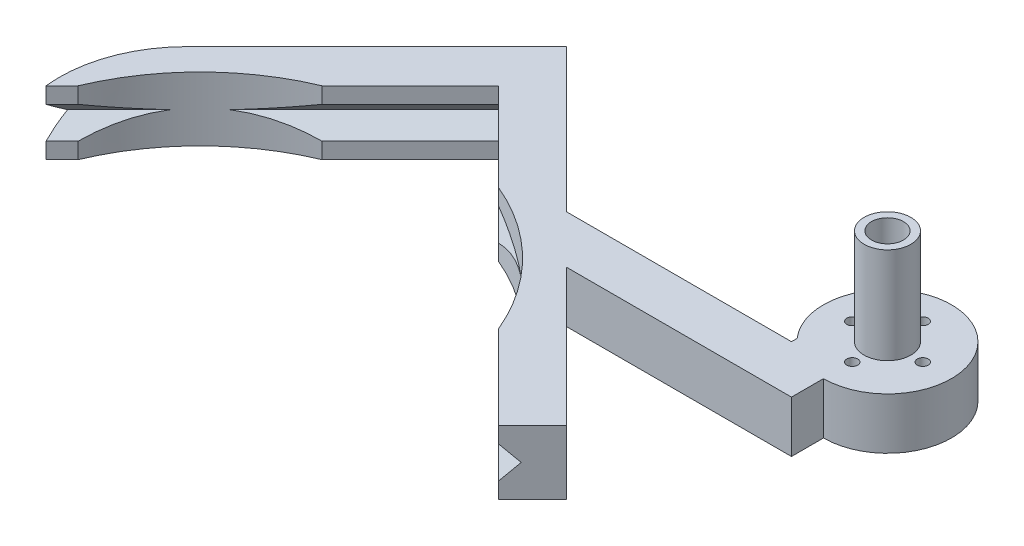
SolidWorks part; units mm, degrees
ref_plane "Front Plane" through (0, 0, 0) normal (0, 0, 1) x (1, 0, 0)
ref_plane "Top Plane" through (0, 0, 0) normal (0, 1, 0) x (1, 0, 0)
ref_plane "Right Plane" through (0, 0, 0) normal (1, 0, 0) x (0, 0, -1)
sketch "Sketch1" plane through (0, 0, 0) normal (0, 1, 0) x (1, 0, 0)
  circle A3 centre (0, -38.254) radius 38.254 construction
  circle A4 centre (0, -40.254) radius 40.254 construction
  circle A5 centre (0, -45.254) radius 45.254 construction
  dimension "D1" = 90.508
  dimension "D2" = 80.508
  dimension "D3" = 76.508
sketch "Sketch3" plane through (0, 0, 0) normal (0, 1, 0) x (1, 0, 0)
  line L8 (58.3717, -39.6268) -> (0, 18.7448)
  line L9 (0, 18.7448) -> (-58.3717, -39.6268)
  line L10 (-58.3717, -39.6268) -> (58.3717, -39.6268) construction
  line L17 (65.1069, -32.8917) -> (37.9076, -5.6924)
  line L18 (0, 32.2152) -> (-65.1069, -32.8917)
  line L19 (-65.1069, -32.8917) -> (-58.3717, -39.6268)
  line L20 (65.1069, -32.8917) -> (58.3717, -39.6268)
  line L23 (82.55, 3.8326) -> (82.55, -5.6924)
  line L26 (65.1069, -32.8917) -> (0, 32.2152) construction
  line L27 (0, 32.2152) -> (-65.1069, -32.8917) construction
  line L28 (28.3826, 3.8326) -> (73.025, 3.8326)
  line L29 (82.55, -5.6924) -> (37.9076, -5.6924)
  line L30 (28.3826, 3.8326) -> (0, 32.2152)
  line L31 (82.55, 3.8326) -> (82.55, 13.3576)
  line L32 (82.55, 13.3576) -> (73.025, 13.3576)
  line L33 (73.025, 13.3576) -> (73.025, 3.8326)
  circle A3 centre (0, -45.254) radius 45.254 construction
  dimension "D1" = 45
  dimension "D2" = 45
  dimension "D3" = 82.55
  dimension "D5" = 9.525
  dimension "D7" = 82.55
  dimension "D6" = 9.525
  dimension "D8" = 52.9844
  dimension "D9" = 9.525
  dimension "D4" = 9.525
extrude "Boss-Extrude1" add sketch "Sketch3" along normal blind 19.05
sketch "Sketch11" plane through (0, 0, 0) normal (0, 1, 0) x (1, 0, 0)
  circle A0 centre (82.55, 13.3576) radius 12.7
  dimension "D1" = 25.4
extrude "Boss-Extrude2" add sketch "Sketch11" along normal blind 19.05
sketch "Sketch14" plane through (0, 0, 0) normal (0, -1, 0) x (1, 0, 0)
  circle A0 centre (89.55, -13.3576) radius 1.077
  circle A2 centre (82.55, -20.3576) radius 1.077
  circle A3 centre (75.55, -13.3576) radius 1.077
  circle A4 centre (82.55, -6.3576) radius 1.077
  circle A5 centre (82.55, -13.3576) radius 12.7 construction
  point P17 (82.55, -13.3576)
  dimension "D2" = 2.154
  dimension "D1" = 7
  dimension "D3" = 4
extrude "Cut-Extrude4" cut sketch "Sketch14" against normal through all
sketch "Sketch16" plane through (0, 0, 0) normal (0, -1, 0) x (1, 0, 0)
  line L2 (37.9076, 5.6924) -> (28.3826, -3.8326)
  line L7 (-65.1069, 32.8917) -> (0, -32.2152)
  line L8 (65.1069, 32.8917) -> (58.3717, 39.6268)
  line L9 (58.3717, 39.6268) -> (0, -18.7448)
  line L10 (0, -18.7448) -> (-58.3717, 39.6268)
  line L20 (-58.3717, 39.6268) -> (-65.1069, 32.8917)
  line L24 (28.3826, -3.8326) -> (73.025, -3.8326)
  line L30 (37.9076, 5.6924) -> (65.1069, 32.8917)
  line L35 (28.3826, -3.8326) -> (73.025, -3.8326)
  line L37 (82.55, 5.6924) -> (37.9076, 5.6924)
  line L38 (82.55, 5.6924) -> (37.9076, 5.6924)
  line L40 (0, -32.2152) -> (28.3826, -3.8326)
  line L47 (82.55, -0.6576) -> (82.55, 5.6924)
  line L48 (82.55, -0.6576) -> (82.55, 5.6924)
  line L49 (73.025, -3.8326) -> (73.025, -4.9573)
  line L50 (73.025, -3.8326) -> (73.025, -4.9573)
  arc A1 (73.025, -4.9573) -> (82.55, -0.6576) centre (82.55, -13.3576) ccw
  arc A6 (73.025, -4.9573) -> (82.55, -0.6576) centre (82.55, -13.3576) ccw
  dimension "D1" = 0
extrude "Cut-Extrude7" cut sketch "Sketch16" against normal blind 8.842
sketch "Sketch17" plane through (0, 19.05, 0) normal (0, 1, 0) x (1, 0, 0)
  line L0 (-65.1069, -32.8917) -> (-51.6365, -19.4213)
  line L1 (0, 32.2152) -> (-65.1069, -32.8917) construction
  line L2 (-51.6365, -19.4213) -> (-44.9013, -26.1565)
  line L3 (-58.3717, -39.6268) -> (0, 18.7448) construction
  line L4 (-44.9013, -26.1565) -> (-58.3717, -39.6268)
  line L5 (-58.3717, -39.6268) -> (-65.1069, -32.8917)
  dimension "D1" = 19.05
extrude "Cut-Extrude8" cut sketch "Sketch17" against normal through all
fillet "Fillet10" radius 25.4 1 edges at (-51.6365, 9.525, 19.4213)
sketch "Sketch18" plane through (0, 19.05, 0) normal (0, 1, 0) x (1, 0, 0)
  circle A0 centre (82.55, 13.3576) radius 3.175
  dimension "D1" = 6.35
extrude "Cut-Extrude9" cut sketch "Sketch18" against normal through all
sketch "Sketch19" plane through (0, 19.05, 0) normal (0, 1, 0) x (1, 0, 0)
  circle A0 centre (82.55, 13.3576) radius 3.175
  circle A1 centre (82.55, 13.3576) radius 4.6355
  dimension "D1" = 9.271
extrude "Boss-Extrude3" add sketch "Sketch19" along normal offset from surface (19.05 mm away) 38.1 up to face at (6.433, 0, 8.7144)
sketch "Sketch20" plane through (0, 0, 0) normal (0, -1, 0) x (1, 0, 0)
  line L5 (0, -18.7448) -> (-44.9013, 26.1565)
  line L6 (-37.6161, 5.4008) -> (0, -32.2152)
  line L7 (0, -32.2152) -> (65.1069, 32.8917)
  line L8 (65.1069, 32.8917) -> (58.3717, 39.6268)
  line L9 (58.3717, 39.6268) -> (0, -18.7448)
  line L10 (0, -18.7448) -> (-44.9013, 26.1565)
  line L11 (-37.6161, 5.4008) -> (0, -32.2152)
  line L12 (0, -32.2152) -> (65.1069, 32.8917)
  line L13 (65.1069, 32.8917) -> (58.3717, 39.6268)
  line L14 (58.3717, 39.6268) -> (0, -18.7448)
  arc A1 (-44.9013, 26.1565) -> (-37.6161, 5.4008) centre (-19.6555, 23.3614) ccw
  arc A3 (-44.9013, 26.1565) -> (-37.6161, 5.4008) centre (-19.6555, 23.3614) ccw
  dimension "D1" = 0
extrude "Cut-Extrude10" cut sketch "Sketch20" against normal blind 6.35
sketch "Sketch21" plane through (48.9993, 0, 48.9993) normal (0.7071, 0, 0.7071) x (0.7071, 0, -0.7071)
  line L0 (13.2546, 15.875) -> (16.4296, 12.7)
  line L1 (13.2546, 19.05) -> (13.2546, 6.35) construction
  line L2 (16.4296, 12.7) -> (13.2546, 9.525)
  line L4 (13.2546, 9.525) -> (13.2546, 15.875)
  point P4 (13.2546, 12.7)
  dimension "D1" = 6.35
extrude "Cut-Extrude11" cut sketch "Sketch21" against normal offset from surface (85.725 mm away) 3.175 up to face at (-22.4506, 12.7, 3.7058) offset beyond the face yes
sketch "Sketch22" plane through (16.1076, 0, -16.1076) normal (0.7071, 0, -0.7071) x (-0.7071, 0, -0.7071)
  line L0 (13.2546, 15.875) -> (13.2546, 9.525)
  line L1 (13.2546, 9.525) -> (16.4296, 12.7)
  line L2 (16.4296, 12.7) -> (13.2546, 15.875)
  line L3 (13.2546, 6.35) -> (13.2546, 19.05) construction
  point P2 (13.2546, 12.7)
  dimension "D1" = 6.35
extrude "Cut-Extrude12" cut sketch "Sketch22" against normal through all from vertex starting at point (0, 12.7, -23.235)
sketch "Sketch23" plane through (0, 19.05, 0) normal (0, 1, 0) x (1, 0, 0)
  circle A2 centre (0, -40.4915) radius 45.254
  circle A3 centre (0, -45.254) radius 45.254 construction
  dimension "D1" = 4.7625
extrude "Cut-Extrude13" cut sketch "Sketch23" against normal through all
equation "\"tightTol\"= 0.005in"
equation "\"normTol\"= 0.01in"
equation "\"looseTol\"= 0.02in"
equation "\"D1@Sketch1\"=\"looseTol\"+9cm"
equation "\"D2@Sketch1\"=8cm+\"looseTol\""
equation "\"D3@Sketch1\"=7.6cm+\"looseTol\""
equation "\"D2\"= 0.875 - 10.7mm"
equation "\"D1\"= 10.7mm"
equation "\"D1@Boss-Extrude1\"=40mm"
equation "\"D2@Sketch14\"= 1.9mm + \"normTol\""
equation "\"D1@Sketch14\"= 7mm"
equation "\"D19@Boss-Extrude2\"=0.250000-1.5*\"normTol\""
equation "\"D1@Boss-Extrude2\"= 0.75"
equation "\"D1@Cut-Extrude7\" = 15.7mm - 0.25 - \"looseTol\""
equation "\"D1@Sketch19\"=0.375000in-\"normTol\""
equation "\"D8@Sketch3\"=4.95-2.864"
